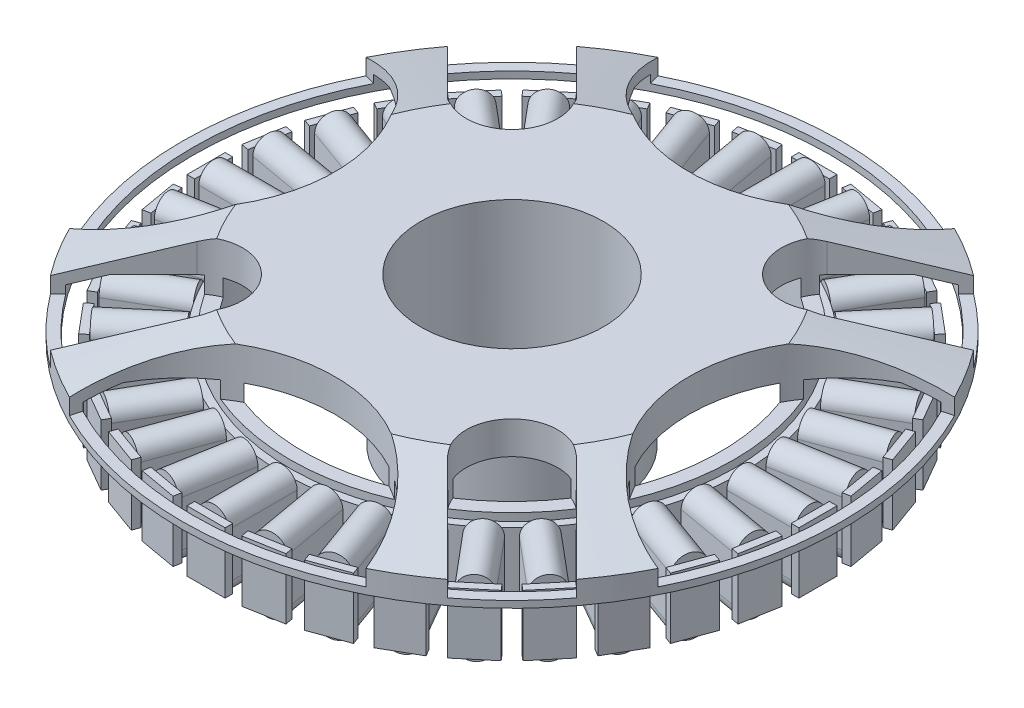
SolidWorks part; units mm, degrees
ref_plane "Front Plane" through (0, 0, 0) normal (0, 0, 1) x (1, 0, 0)
ref_plane "Top Plane" through (0, 0, 0) normal (0, 1, 0) x (1, 0, 0)
ref_plane "Right Plane" through (0, 0, 0) normal (1, 0, 0) x (0, 0, -1)
sketch "Sketch1" plane through (0, 0, 0) normal (0, 1, 0) x (1, 0, 0)
  circle A0 centre (0, 0) radius 43.25
  circle A1 centre (0, 0) radius 41.85
  point P5 (0, -2.3324)
  dimension "D1" = 86.5
  dimension "D2" = 1.4
extrude "Boss-Extrude1" add sketch "Sketch1" along normal blind 1.5
sketch "Sketch2" plane through (0, 0, 0) normal (0, 0, 1) x (1, 0, 0)
  line L0 (0, 7.4) -> (-28, 7.4)
  line L1 (-43.25, 1.5) -> (-43.25, 3)
  line L2 (-43.25, 0) -> (43.25, 0) construction
  line L3 (0, 7.4) -> (0, 3.1)
  line L4 (0, 3.1) -> (-37.8532, 3.1)
  line L5 (-41.85, 1.5) -> (-41.85, 1.9468)
  line L6 (-43.25, 1.5) -> (-41.85, 1.5)
  line L8 (-43.25, 3) -> (-28, 7.4)
  line L9 (-41.85, 1.9468) -> (-37.8532, 3.1)
  dimension "D1" = 28
  dimension "D2" = 7.4
  dimension "D3" = 4.3
  dimension "D4" = 1.5
  dimension "D5" = 1.4
revolve "Revolve1" add sketch "Sketch2" angle 360 about L3
sketch "Sketch3" plane through (0, 3.1, 0) normal (0, -1, 0) x (1, 0, 0)
  circle A0 centre (0, 0) radius 13.5
  dimension "D1" = 27
extrude "Boss-Extrude2" add sketch "Sketch3" along normal blind 15
sketch "Sketch4" plane through (0, -11.9, 0) normal (0, -1, 0) x (1, 0, 0)
  circle A0 centre (0, 0) radius 7.5
  dimension "D1" = 15
extrude "Boss-Extrude3" add sketch "Sketch4" along normal blind 18
sketch "Sketch5" plane through (0, 7.4, 0) normal (0, 1, 0) x (1, 0, 0)
  circle A0 centre (0, 0) radius 6.6
  dimension "D1" = 13.2
extrude "Cut-Extrude1" cut sketch "Sketch5" against normal blind 20
sketch "Sketch6" plane through (0, -29.9, 0) normal (0, -1, 0) x (1, 0, 0)
  circle A0 centre (0, 0) radius 2.5
  dimension "D1" = 5
extrude "Cut-Extrude2" cut sketch "Sketch6" against normal through all
sketch "Sketch7" plane through (0, 7.4, 0) normal (0, 1, 0) x (1, 0, 0)
  line L0 (-30.5824, 30.5824) -> (-20.6829, 20.6829) construction
  line L1 (-26.3397, 34.825) -> (-16.4402, 24.9255)
  line L2 (-34.825, 26.3397) -> (-24.9255, 16.4402)
  line L3 (-20.6829, 20.6829) -> (0, 0) construction
  line L4 (0, 43.25) -> (0, 0) construction
  line L5 (26.3397, 34.825) -> (16.4402, 24.9255)
  line L6 (34.825, 26.3397) -> (24.9255, 16.4402)
  line L7 (30.5824, 30.5824) -> (20.6829, 20.6829) construction
  line L8 (34.825, -26.3397) -> (24.9255, -16.4402)
  line L9 (26.3397, -34.825) -> (16.4402, -24.9255)
  line L10 (30.5824, -30.5824) -> (20.6829, -20.6829) construction
  line L11 (-26.3397, -34.825) -> (-16.4402, -24.9255)
  line L12 (-34.825, -26.3397) -> (-24.9255, -16.4402)
  line L13 (-30.5824, -30.5824) -> (-20.6829, -20.6829) construction
  circle A0 centre (0, 43.25) radius 20
  circle A1 centre (0, 0) radius 43.25 construction
  circle A2 centre (43.25, 0) radius 20
  circle A3 centre (0, -43.25) radius 20
  circle A4 centre (-43.25, 0) radius 20
  arc A5 (-26.3397, 34.825) -> (-34.825, 26.3397) centre (-30.5824, 30.5824) ccw
  arc A6 (-24.9255, 16.4402) -> (-16.4402, 24.9255) centre (-20.6829, 20.6829) ccw
  arc A7 (34.825, 26.3397) -> (26.3397, 34.825) centre (30.5824, 30.5824) ccw
  arc A8 (16.4402, 24.9255) -> (24.9255, 16.4402) centre (20.6829, 20.6829) ccw
  arc A9 (26.3397, -34.825) -> (34.825, -26.3397) centre (30.5824, -30.5824) ccw
  arc A10 (24.9255, -16.4402) -> (16.4402, -24.9255) centre (20.6829, -20.6829) ccw
  arc A11 (-34.825, -26.3397) -> (-26.3397, -34.825) centre (-30.5824, -30.5824) ccw
  arc A12 (-16.4402, -24.9255) -> (-24.9255, -16.4402) centre (-20.6829, -20.6829) ccw
  point P4 (-25.6326, 25.6326)
  point P14 (0, 0)
  point P22 (-25.0316, -28.7196)
  point P23 (0, 0)
  point P25 (25.6326, 25.6326)
  point P32 (25.6326, -25.6326)
  point P39 (-25.6326, -25.6326)
  point P46 (0, 0)
  dimension "D1" = 40
  dimension "D4" = 6
  dimension "D3" = 45
  dimension "D5" = 14
  dimension "D2" = 4
  dimension "D6" = 4
extrude "Cut-Extrude3" cut sketch "Sketch7" against normal blind 6.5
sketch "Sketch8" plane through (0, 7.4, 0) normal (0, 1, 0) x (1, 0, 0)
  circle A0 centre (0, 0) radius 12
  dimension "D1" = 24
extrude "Cut-Extrude4" cut sketch "Sketch8" against normal through all
ref_plane "Plane1" through (0, 0.9, 0) normal (0, 1, 0) x (1, 0, 0)
sketch "Sketch10" plane through (0, 0.9, 0) normal (0, 1, 0) x (1, 0, 0)
  circle A0 centre (0, 0) radius 29.15
  circle A1 centre (0, 0) radius 27.35
  dimension "D1" = 58.3
  dimension "D2" = 1.8
extrude "Boss-Extrude4" add sketch "Sketch10" against normal blind 10 separate body
sketch "Sketch11" plane through (0, 0.9, 0) normal (0, 1, 0) x (1, 0, 0)
  line L0 (24.9255, -16.4402) -> (34.5293, -26.044) construction
  line L1 (26.044, -34.5293) -> (16.4402, -24.9255) construction
  line L2 (-16.4402, -24.9255) -> (-26.044, -34.5293) construction
  line L3 (-34.5293, -26.044) -> (-24.9255, -16.4402) construction
  line L4 (-24.9255, 16.4402) -> (-34.5293, 26.044) construction
  line L5 (-26.044, 34.5293) -> (-16.4402, 24.9255) construction
  line L6 (16.4402, 24.9255) -> (26.044, 34.5293) construction
  line L7 (34.5293, 26.044) -> (24.9255, 16.4402) construction
  line L8 (24.9255, -16.4402) -> (34.5293, -26.044)
  line L9 (26.044, -34.5293) -> (16.4402, -24.9255)
  line L10 (-16.4402, -24.9255) -> (-26.044, -34.5293)
  line L11 (-34.5293, -26.044) -> (-24.9255, -16.4402)
  line L12 (-24.9255, 16.4402) -> (-34.5293, 26.044)
  line L13 (-26.044, 34.5293) -> (-16.4402, 24.9255)
  line L14 (16.4402, 24.9255) -> (26.044, 34.5293)
  line L15 (34.5293, 26.044) -> (24.9255, 16.4402)
  arc A0 (26.0643, -10.23) -> (38.6257, -19.4581) centre (43.25, 0) ccw construction
  circle A1 centre (0, 0) radius 29.15
  circle A2 centre (0, 0) radius 29.15
  arc A4 (24.9255, -16.4402) -> (23.4213, -15.3442) centre (20.6829, -20.6829) ccw construction
  arc A5 (34.5293, -26.044) -> (38.6257, -19.4581) centre (0, 0) ccw construction
  arc A6 (19.4581, -38.6257) -> (10.23, -26.0643) centre (0, -43.25) ccw construction
  arc A7 (19.4581, -38.6257) -> (26.044, -34.5293) centre (0, 0) ccw construction
  arc A8 (15.3442, -23.4213) -> (16.4402, -24.9255) centre (20.6829, -20.6829) ccw construction
  arc A10 (-10.23, -26.0643) -> (-19.4581, -38.6257) centre (0, -43.25) ccw construction
  arc A12 (-16.4402, -24.9255) -> (-15.3442, -23.4213) centre (-20.6829, -20.6829) ccw construction
  arc A13 (-26.044, -34.5293) -> (-19.4581, -38.6257) centre (0, 0) ccw construction
  arc A14 (-38.6257, -19.4581) -> (-26.0643, -10.23) centre (-43.25, 0) ccw construction
  arc A15 (-38.6257, -19.4581) -> (-34.5293, -26.044) centre (0, 0) ccw construction
  arc A16 (-23.4213, -15.3442) -> (-24.9255, -16.4402) centre (-20.6829, -20.6829) ccw construction
  arc A17 (-26.0643, -10.23) -> (-23.4213, -15.3442) centre (0, 0) ccw construction
  arc A18 (-26.0643, -10.23) -> (-26.0643, 10.23) centre (-43.25, 0) ccw
  arc A19 (-26.0643, -10.23) -> (-23.4213, -15.3442) centre (0, 0) ccw
  arc A20 (-15.3442, -23.4213) -> (-23.4213, -15.3442) centre (-20.6829, -20.6829) ccw
  arc A21 (-15.3442, -23.4213) -> (-10.23, -26.0643) centre (0, 0) ccw
  arc A22 (10.23, -26.0643) -> (-10.23, -26.0643) centre (0, -43.25) ccw
  arc A23 (10.23, -26.0643) -> (15.3442, -23.4213) centre (0, 0) ccw
  arc A24 (23.4213, -15.3442) -> (15.3442, -23.4213) centre (20.6829, -20.6829) ccw
  arc A25 (23.4213, -15.3442) -> (26.0643, -10.23) centre (0, 0) ccw
  arc A26 (26.0643, 10.23) -> (26.0643, -10.23) centre (43.25, 0) ccw
  arc A27 (26.0643, 10.23) -> (23.4213, 15.3442) centre (0, 0) ccw
  arc A28 (15.3442, 23.4213) -> (23.4213, 15.3442) centre (20.6829, 20.6829) ccw
  arc A29 (15.3442, 23.4213) -> (10.23, 26.0643) centre (0, 0) ccw
  arc A30 (-10.23, 26.0643) -> (10.23, 26.0643) centre (0, 43.25) ccw
  arc A31 (-10.23, 26.0643) -> (-15.3442, 23.4213) centre (0, 0) ccw
  arc A32 (-23.4213, 15.3442) -> (-15.3442, 23.4213) centre (-20.6829, 20.6829) ccw
  arc A33 (-23.4213, 15.3442) -> (-26.0643, 10.23) centre (0, 0) ccw
  arc A34 (-26.0643, -10.23) -> (-26.0643, 10.23) centre (-43.25, 0) ccw
  arc A35 (-26.0643, -10.23) -> (-23.4213, -15.3442) centre (0, 0) ccw
  arc A36 (-15.3442, -23.4213) -> (-23.4213, -15.3442) centre (-20.6829, -20.6829) ccw
  arc A38 (10.23, -26.0643) -> (-10.23, -26.0643) centre (0, -43.25) ccw
  arc A40 (23.4213, -15.3442) -> (15.3442, -23.4213) centre (20.6829, -20.6829) ccw
  arc A42 (26.0643, 10.23) -> (26.0643, -10.23) centre (43.25, 0) ccw
  arc A44 (15.3442, 23.4213) -> (23.4213, 15.3442) centre (20.6829, 20.6829) ccw
  arc A46 (-10.23, 26.0643) -> (10.23, 26.0643) centre (0, 43.25) ccw
  arc A48 (-23.4213, 15.3442) -> (-15.3442, 23.4213) centre (-20.6829, 20.6829) ccw
  arc A50 (-26.0643, 10.23) -> (-38.6257, 19.4581) centre (-43.25, 0) ccw construction
  arc A52 (-24.9255, 16.4402) -> (-23.4213, 15.3442) centre (-20.6829, 20.6829) ccw construction
  arc A53 (-34.5293, 26.044) -> (-38.6257, 19.4581) centre (0, 0) ccw construction
  arc A54 (-15.3442, 23.4213) -> (-16.4402, 24.9255) centre (-20.6829, 20.6829) ccw construction
  arc A56 (-19.4581, 38.6257) -> (-10.23, 26.0643) centre (0, 43.25) ccw construction
  arc A57 (-19.4581, 38.6257) -> (-26.044, 34.5293) centre (0, 0) ccw construction
  arc A58 (16.4402, 24.9255) -> (15.3442, 23.4213) centre (20.6829, 20.6829) ccw construction
  arc A59 (26.044, 34.5293) -> (19.4581, 38.6257) centre (0, 0) ccw construction
  arc A60 (10.23, 26.0643) -> (19.4581, 38.6257) centre (0, 43.25) ccw construction
  arc A62 (38.6257, 19.4581) -> (26.0643, 10.23) centre (43.25, 0) ccw construction
  arc A63 (38.6257, 19.4581) -> (34.5293, 26.044) centre (0, 0) ccw construction
  arc A64 (23.4213, 15.3442) -> (24.9255, 16.4402) centre (20.6829, 20.6829) ccw construction
  arc A66 (26.0643, -10.23) -> (38.6257, -19.4581) centre (43.25, 0) ccw
  arc A68 (24.9255, -16.4402) -> (23.4213, -15.3442) centre (20.6829, -20.6829) ccw
  arc A69 (34.5293, -26.044) -> (38.6257, -19.4581) centre (0, 0) ccw
  arc A70 (19.4581, -38.6257) -> (10.23, -26.0643) centre (0, -43.25) ccw
  arc A71 (19.4581, -38.6257) -> (26.044, -34.5293) centre (0, 0) ccw
  arc A72 (15.3442, -23.4213) -> (16.4402, -24.9255) centre (20.6829, -20.6829) ccw
  arc A74 (-10.23, -26.0643) -> (-19.4581, -38.6257) centre (0, -43.25) ccw
  arc A76 (-16.4402, -24.9255) -> (-15.3442, -23.4213) centre (-20.6829, -20.6829) ccw
  arc A77 (-26.044, -34.5293) -> (-19.4581, -38.6257) centre (0, 0) ccw
  arc A78 (-38.6257, -19.4581) -> (-26.0643, -10.23) centre (-43.25, 0) ccw
  arc A79 (-38.6257, -19.4581) -> (-34.5293, -26.044) centre (0, 0) ccw
  arc A80 (-23.4213, -15.3442) -> (-24.9255, -16.4402) centre (-20.6829, -20.6829) ccw
  arc A81 (-26.0643, -10.23) -> (-23.4213, -15.3442) centre (0, 0) ccw
  arc A82 (-26.0643, 10.23) -> (-38.6257, 19.4581) centre (-43.25, 0) ccw
  arc A84 (-24.9255, 16.4402) -> (-23.4213, 15.3442) centre (-20.6829, 20.6829) ccw
  arc A85 (-34.5293, 26.044) -> (-38.6257, 19.4581) centre (0, 0) ccw
  arc A86 (-15.3442, 23.4213) -> (-16.4402, 24.9255) centre (-20.6829, 20.6829) ccw
  arc A88 (-19.4581, 38.6257) -> (-10.23, 26.0643) centre (0, 43.25) ccw
  arc A89 (-19.4581, 38.6257) -> (-26.044, 34.5293) centre (0, 0) ccw
  arc A90 (16.4402, 24.9255) -> (15.3442, 23.4213) centre (20.6829, 20.6829) ccw
  arc A91 (26.044, 34.5293) -> (19.4581, 38.6257) centre (0, 0) ccw
  arc A92 (10.23, 26.0643) -> (19.4581, 38.6257) centre (0, 43.25) ccw
  arc A94 (38.6257, 19.4581) -> (26.0643, 10.23) centre (43.25, 0) ccw
  arc A95 (38.6257, 19.4581) -> (34.5293, 26.044) centre (0, 0) ccw
  arc A96 (23.4213, 15.3442) -> (24.9255, 16.4402) centre (20.6829, 20.6829) ccw
  circle A98 centre (0, 0) radius 27.35 construction
  circle A99 centre (0, 0) radius 27.35
  circle M39 centre (0, 0) radius 27.35
  dimension "D1" = 0
  dimension "D2" = 0
extrude "Boss-Extrude5" add sketch "Sketch11" along normal up to surface (2.2 mm away) contours A76 A2 A74 A38 A36 M39 | A72 A40 A38 A70 A2 M39 | A68 A2 A66 A42 A40 M39 | A96 A44 A42 A94 A2 M39 | A92 A46 A44 A90 A2 M39 | A88 A2 A86 A48 A46 M39 | A84 A2 A82 A34 A48 M39 | A80 A35 A78 A2 | A36 A34 A35 M39
ref_plane "Plane2" through (0, -8.1, 0) normal (0, -1, 0) x (-1, 0, 0)
sketch "Sketch12" plane through (0, -8.1, 0) normal (0, -1, 0) x (-1, 0, 0)
  line L0 (0, 29.15) -> (0, 40.15) construction
  line L1 (-2.5, 40.15) -> (2.5, 40.15)
  line L2 (-2.5, 40.15) -> (-2.5, 39.15)
  line L3 (-2.5, 39.15) -> (-0.5, 39.15)
  line L4 (-0.5, 39.15) -> (-0.5, 29.1457)
  line L5 (2.5, 40.15) -> (2.5, 39.15)
  line L6 (2.5, 39.15) -> (0.5, 39.15)
  line L7 (0.5, 39.15) -> (0.5, 29.1457)
  circle A0 centre (0, 0) radius 29.15 construction
  arc A1 (0.5, 29.1457) -> (-0.5, 29.1457) centre (0, 0) ccw
  point P6 (-0.5, 29.15)
  point P9 (0, 40.15)
  dimension "D1" = 11
  dimension "D2" = 5
  dimension "D3" = 1
  dimension "D4" = 1
  dimension "D5" = 0.5
  dimension "D6" = 0.5
extrude "Boss-Extrude6" add sketch "Sketch12" against normal blind 8
sketch "Sketch13" plane through (0, 0, -39.15) normal (0, 0, 1) x (1, 0, 0)
  line L0 (-2.5, -0.1) -> (2.5, -0.1) construction
  line L1 (-2.5, -8.1) -> (2.5, -8.1) construction
  line L2 (-2.5, -0.1) -> (2.5, -0.1)
  line L3 (-2.5, -8.1) -> (2.5, -8.1)
  line L4 (0, -1.1) -> (0, -7.1) construction
  line L5 (1.95, -1.1) -> (1.95, -7.1)
  line L6 (-1.95, -1.1) -> (-1.95, -7.1)
  arc A0 (1.95, -1.1) -> (-1.95, -1.1) centre (0, -1.1) ccw
  arc A1 (-1.95, -7.1) -> (1.95, -7.1) centre (0, -7.1) ccw
  point P7 (0, -4.1)
  dimension "D1" = 1.95
  dimension "D2" = 1
  dimension "D3" = 1
extrude "Boss-Extrude7" add sketch "Sketch13" along normal blind 9
pattern_circular "CirPattern1" count 36 over 360 about axis through (0, 0, 0) along (0, 1, 0) of "Boss-Extrude6"
sketch "Sketch14" plane through (0, -8.1, 0) normal (0, -1, 0) x (1, 0, 0)
  circle A0 centre (0, 0) radius 30.15
  circle A1 centre (0, 0) radius 29.15 construction
  circle A2 centre (0, 0) radius 29.15
  dimension "D1" = 1
extrude "Boss-Extrude8" add sketch "Sketch14" against normal up to vertex
pattern_circular "CirPattern2" count 36 over 360 about axis through (0, 0, 0) along (0, 1, 0) of "Boss-Extrude7"
